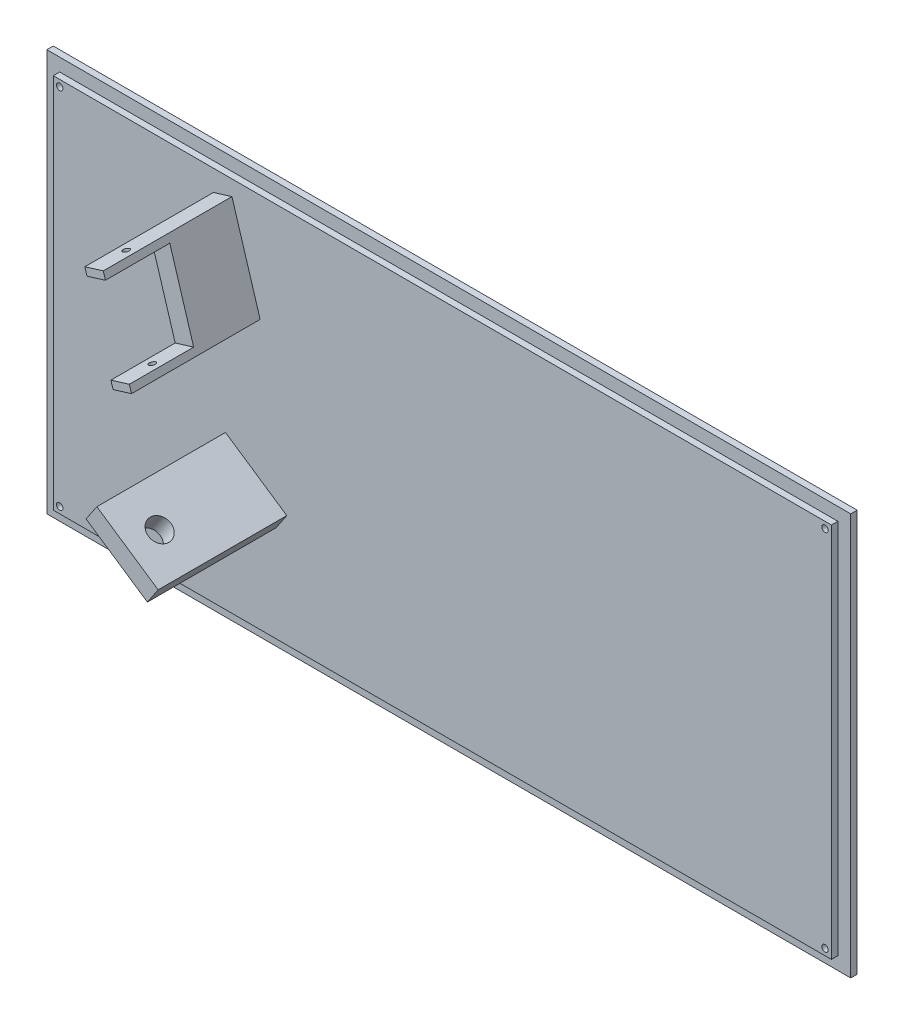
SolidWorks part; units mm, degrees
ref_plane "Ebene vorne" through (0, 0, 0) normal (0, 0, 1) x (1, 0, 0)
ref_plane "Ebene oben" through (0, 0, 0) normal (0, 1, 0) x (1, 0, 0)
ref_plane "Ebene rechts" through (0, 0, 0) normal (1, 0, 0) x (0, 0, -1)
sketch "Skizze1" plane through (0, 0, 0) normal (0, 0, 1) x (1, 0, 0)
  line L1 (0, 125) -> (250, 125)
  line L2 (0, 125) -> (0, 0)
  line L3 (0, 0) -> (250, 0)
  line L4 (250, 125) -> (250, 0)
  dimension "D1" = 250
  dimension "D2" = 125
extrude "Aufsatz-Linear austragen1" add sketch "Skizze1" along normal blind 2 contours L2 L1 L4 L3
sketch "Skizze2" plane through (0, 0, 2) normal (0, 0, 1) x (1, 0, 0)
  line L0 (0, 125) -> (0, 0) construction
  line L1 (4, 121) -> (246, 121)
  line L2 (4, 121) -> (4, 4)
  line L3 (4, 4) -> (246, 4)
  line L4 (246, 121) -> (246, 4)
  line L5 (0, 125) -> (250, 125) construction
  line L6 (0, 0) -> (250, 0) construction
  line L7 (250, 125) -> (250, 0) construction
  dimension "D1" = 4
  dimension "D2" = 4
  dimension "D3" = 4
  dimension "D4" = 4
extrude "Aufsatz-Linear austragen2" add sketch "Skizze2" along normal blind 2
sketch "Skizze3" plane through (0, 0, 4) normal (0, 0, 1) x (1, 0, 0)
  line L0 (246, 121) -> (4, 121) construction
  line L1 (4, 121) -> (4, 4) construction
  line L2 (4, 121) -> (4, 4) construction
  line L3 (4, 4) -> (246, 4) construction
  line L4 (246, 4) -> (246, 121) construction
  line L5 (246, 121) -> (4, 121) construction
  circle A0 centre (6, 119) radius 1
  circle A1 centre (6, 6) radius 1
  circle A2 centre (244, 6) radius 1
  circle A3 centre (244, 119) radius 1
  dimension "D1" = 2
  dimension "D3" = 2
  dimension "D5" = 2
  dimension "D2" = 2
  dimension "D4" = 2
  dimension "D6" = 2
  dimension "D7" = 2
  dimension "D8" = 2
extrude "Schnitt-Linear austragen1" cut sketch "Skizze3" against normal blind 32
sketch "Skizze4" plane through (0, 0, 4) normal (0, 0, 1) x (1, 0, 0)
  line L0 (246, 121) -> (246, 4) construction
  line L1 (4, 62.5) -> (246, 62.5) construction
  line L3 (4, 121) -> (4, 4) construction
  line L4 (4, 62.5) -> (90.7298, 121) construction
  line L5 (3.8274, 56.5) -> (246, 56.5) construction
  line L6 (246, 121) -> (4, 121) construction
  line L15 (4, 62.5) -> (90.7298, 4) construction
  line L16 (4, 4) -> (246, 4) construction
  line L17 (3.8274, 56.5) -> (3.8274, 68.5) construction
  line L18 (4, 62.5) -> (195.3449, 121) construction
  line L26 (3.8274, 68.5) -> (246, 68.5) construction
  line L31 (62.5953, 85.7783) -> (68.3331, 87.5325)
  line L32 (62.5953, 85.7783) -> (53.8241, 114.4675)
  line L33 (68.3331, 87.5325) -> (59.5619, 116.2217)
  line L34 (53.8241, 114.4675) -> (59.5619, 116.2217)
  line L35 (53.8241, 114.4675) -> (68.3331, 87.5325) construction
  line L36 (246, 121) -> (4, 121) construction
  line L37 (37.4248, 21.8614) -> (54.2006, 46.7326) construction
  line L38 (54.2006, 46.7326) -> (73.2684, 33.8711) construction
  line L39 (37.4248, 21.8614) -> (56.4926, 9) construction
  line L40 (56.4926, 9) -> (73.2684, 33.8711) construction
  line L41 (54.2006, 46.7326) -> (73.2684, 33.8711)
  line L42 (54.2006, 46.7326) -> (57.5557, 51.7068)
  line L43 (73.2684, 33.8711) -> (76.6236, 38.8454)
  line L44 (57.5557, 51.7068) -> (76.6236, 38.8454)
  point P11 (3.8274, 62.5)
  point P14 (61.0786, 101)
  point P27 (45.8127, 34.297)
  dimension "D1" = 34
  dimension "D2" = 34
  dimension "D3" = 12
  dimension "D4" = 17
  dimension "D5" = 6
  dimension "D6" = 30
  dimension "D7" = 20
  dimension "D8" = 30
  dimension "D9" = 23
  dimension "D10" = 6
  dimension "D11" = 5
extrude "Aufsatz-Linear austragen3" add sketch "Skizze4" along normal blind 40
sketch "Skizze7" plane through (0, 0, 44) normal (0, 0, 1) x (1, 0, 0)
  line L0 (54.4966, 112.268) -> (60.2344, 114.0222)
  line L1 (54.4966, 112.268) -> (61.9228, 87.9778)
  line L2 (60.2344, 114.0222) -> (67.6606, 89.732)
  line L3 (61.9228, 87.9778) -> (67.6606, 89.732)
  line L4 (53.8241, 114.4675) -> (62.5953, 85.7783) construction
  line L5 (68.3331, 87.5325) -> (59.5619, 116.2217) construction
  line L6 (57.3655, 113.1451) -> (56.693, 115.3446) construction
  line L7 (59.5619, 116.2217) -> (53.8241, 114.4675) construction
  line L8 (64.7917, 88.8549) -> (65.4642, 86.6554) construction
  line L9 (62.5953, 85.7783) -> (68.3331, 87.5325) construction
  dimension "D1" = 25.4
extrude "Schnitt-Linear austragen2" cut sketch "Skizze7" against normal blind 20
sketch "Skizze8" plane through (-27.4037, 89.6336, 0) normal (-0.2924, 0.9563, 0) x (0.9563, 0.2924, 0)
  line L0 (90.9393, -44) -> (90.9393, -4) construction
  line L1 (90.9393, -4) -> (84.9393, -4) construction
  circle A0 centre (87.9393, -34) radius 1
  dimension "D1" = 3
  dimension "D2" = 30
extrude "Schnitt-Linear austragen3" cut sketch "Skizze8" against normal blind 40
sketch "Skizze9" plane through (41.9683, 62.2206, 0) normal (0.5592, 0.829, 0) x (0.829, -0.5592, 0)
  line L0 (30.3018, -34) -> (18.8018, -34) construction
  line L1 (18.8018, -44) -> (18.8018, -4) construction
  line L2 (30.3018, -34) -> (41.8018, -34) construction
  line L3 (41.8018, -44) -> (41.8018, -4) construction
  line L4 (41.8018, -4) -> (18.8018, -4) construction
  circle A0 centre (30.3018, -34) radius 3.4931
  dimension "D1" = 30
extrude "Schnitt-Linear austragen4" cut sketch "Skizze9" against normal blind 20
